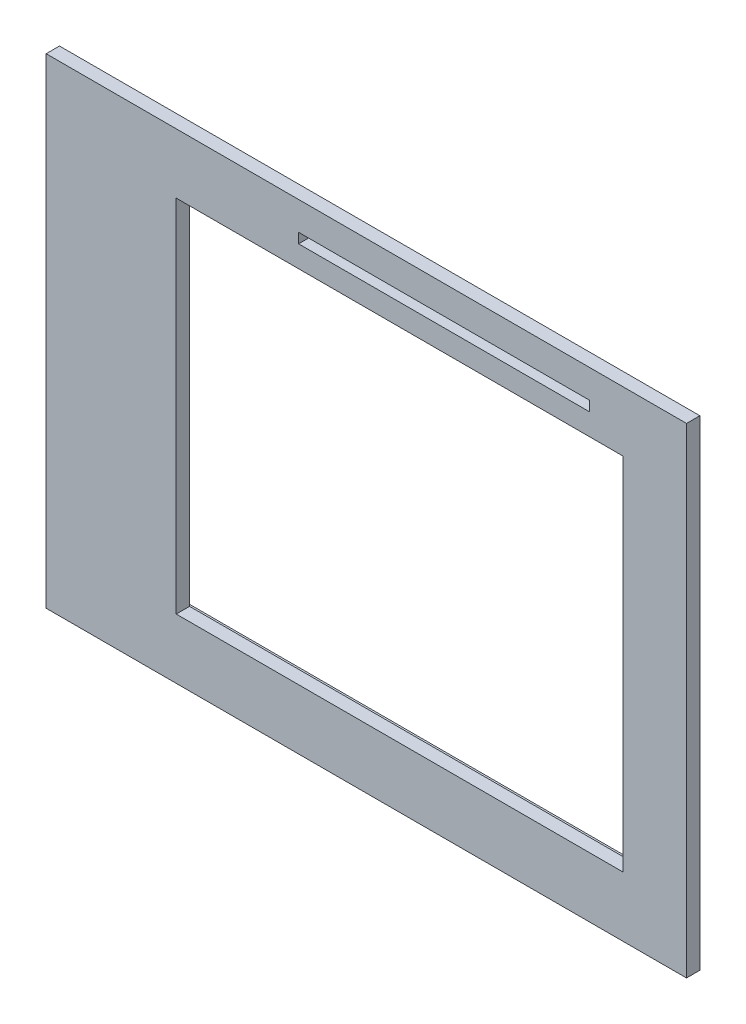
SolidWorks part; units mm, degrees
ref_plane "Front Plane" through (0, 0, 0) normal (0, 0, 1) x (1, 0, 0)
ref_plane "Top Plane" through (0, 0, 0) normal (0, 1, 0) x (1, 0, 0)
ref_plane "Right Plane" through (0, 0, 0) normal (1, 0, 0) x (0, 0, -1)
sketch "Sketch1" plane through (0, 0, 0) normal (0, 0, 1) x (1, 0, 0)
  line L0 (77.0796, 48.6854) -> (-18.9204, -23.3146) construction
  line L1 (-18.9204, 48.6854) -> (77.0796, 48.6854)
  line L2 (-18.9204, 48.6854) -> (-18.9204, -23.3146)
  line L3 (-18.9204, -23.3146) -> (77.0796, -23.3146)
  line L4 (77.0796, 48.6854) -> (77.0796, -23.3146)
  line L5 (-18.9204, 48.6854) -> (77.0796, -23.3146) construction
  line L6 (-18.9204, 12.6854) -> (77.0796, 12.6854) construction
  line L12 (0.5796, -14.3146) -> (67.5796, -14.3146)
  line L13 (0.5796, -14.3146) -> (0.5796, 39.6854)
  line L14 (0.5796, 39.6854) -> (67.5796, 39.6854)
  line L15 (67.5796, -14.3146) -> (67.5796, 39.6854)
  line L16 (0.5796, -14.3146) -> (67.5796, 39.6854) construction
  line L17 (0.5796, 39.6854) -> (67.5796, -14.3146) construction
  point P4 (29.0796, 12.6854)
  point P5 (40.2386, 12.6854)
  point P8 (29.0796, 12.6854)
  point P9 (34.0796, 12.6854)
  dimension "D1" = 96
  dimension "D2" = 72
  dimension "D3" = 67
  dimension "D4" = 54
  dimension "D5" = 5
extrude "Boss-Extrude1" add sketch "Sketch1" along normal blind 2
sketch "Sketch2" plane through (0, 0, 0) normal (0, 0, -1) x (-1, 0, 0)
  line L0 (-77.0796, 48.6854) -> (18.9204, -23.3146) construction
  line L1 (18.9204, 48.6854) -> (-77.0796, -23.3146) construction
  line L7 (-67.0796, -15.8146) -> (8.9204, 41.1854) construction
  line L8 (-67.0796, 41.1854) -> (8.9204, -15.8146) construction
  line L9 (-77.0796, 12.6854) -> (18.9204, 12.6854) construction
  line L14 (-70.4872, -18.3703) -> (12.328, 43.7411) construction
  line L15 (-70.4872, 43.7411) -> (12.328, -18.3703) construction
  line L16 (18.9204, 48.6854) -> (18.9204, -23.3146) construction
  line L17 (-0.5796, 39.6854) -> (-0.5796, -14.3146) construction
  line L22 (-0.5796, -14.3146) -> (-67.5796, -14.3146) construction
  line L23 (-67.5796, -14.3146) -> (-67.5796, 39.6854) construction
  line L24 (-67.5796, 39.6854) -> (-0.5796, 39.6854) construction
  line L25 (-0.5796, 39.6854) -> (-0.5796, -14.3146) construction
  line L26 (-0.5796, -14.3146) -> (-67.5796, -14.3146) construction
  line L27 (-67.5796, -14.3146) -> (-67.5796, 39.6854) construction
  line L28 (-67.5796, 39.6854) -> (-0.5796, 39.6854) construction
  line L29 (-67.5796, 39.6854) -> (-0.5796, -14.3146) construction
  line L30 (-0.5796, 39.6854) -> (-67.5796, -14.3146) construction
  line L32 (4.674, -16.5478) -> (-72.8332, -16.5478)
  line L33 (4.674, -16.5478) -> (4.674, 41.9187)
  line L34 (4.674, 41.9187) -> (-72.8332, 41.9187)
  line L35 (-72.8332, -16.5478) -> (-72.8332, 41.9187)
  line L36 (4.674, -16.5478) -> (-72.8332, 41.9187) construction
  line L37 (4.674, 41.9187) -> (-72.8332, -16.5478) construction
  point P8 (-29.0796, 12.6854)
  point P15 (-29.0796, 12.6854)
  point P23 (-29.0796, 12.6854)
  point P24 (-34.0796, 12.6854)
  point P26 (-34.0796, 12.6854)
sketch "Sketch3" plane through (0, 0, 2) normal (0, 0, 1) x (1, 0, 0)
  line L0 (62.5693, 43.6733) -> (18.9229, 43.6733)
extrude "Cut-Extrude-Thin1" cut sketch "Sketch3" against normal through all and the other way through all thin thin type mid plane wall 1.5
extrude "Extrude-Thin3" add sketch "Sketch2" along normal blind 2 thin thin type mid plane wall 1
sketch "Sketch4" plane through (0, 0, 0) normal (0, 0, -1) x (-1, 0, 0)
  text T0 "THIS SIDE FACING CAMERA" font "Century Gothic" height 3.175
